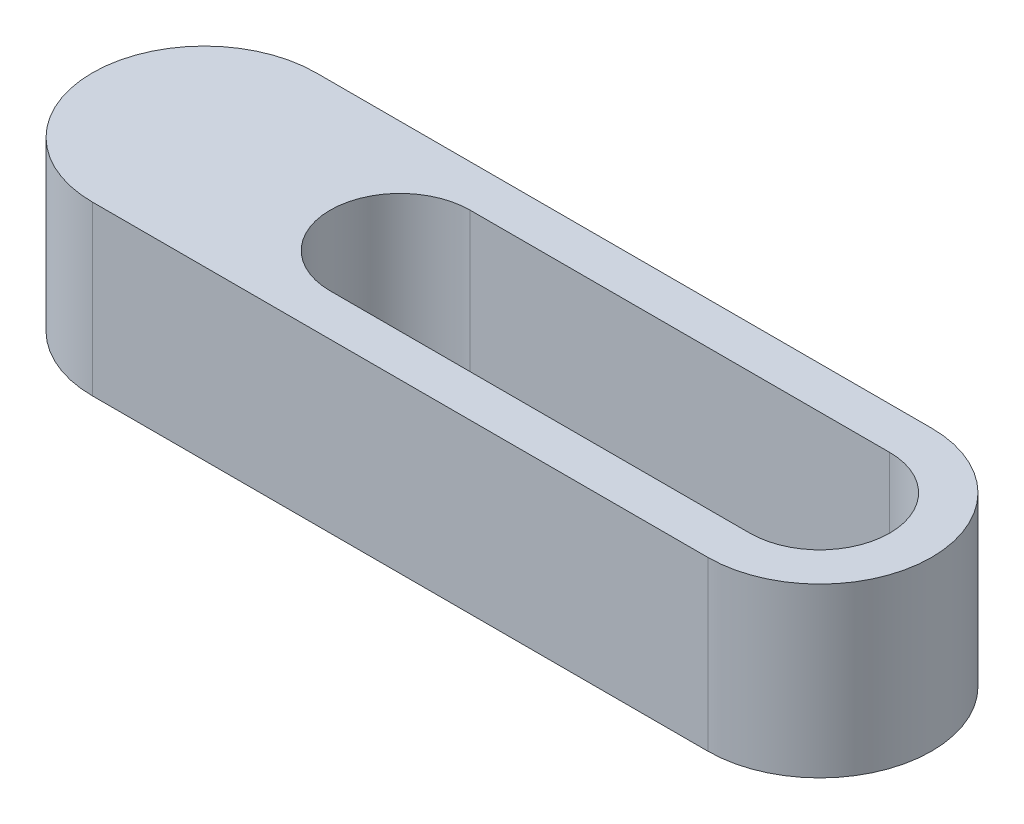
SolidWorks part; units mm, degrees
ref_plane "Ön Düzlem" through (0, 0, 0) normal (0, 0, 1) x (1, 0, 0)
ref_plane "Üst Düzlem" through (0, 0, 0) normal (0, 1, 0) x (1, 0, 0)
ref_plane "Sağ Düzlem" through (0, 0, 0) normal (1, 0, 0) x (0, 0, -1)
sketch "Çizim1" plane through (0, 0, 0) normal (0, 1, 0) x (1, 0, 0)
  line L1 (-5.5, 11.25) -> (5.5, 11.25)
  line L2 (-6, 10.75) -> (-6, -10.75)
  line L3 (-5.5, -11.25) -> (5.5, -11.25)
  line L4 (6, 10.75) -> (6, -10.75)
  line L5 (-6, 11.25) -> (6, -11.25) construction
  line L6 (-6, -11.25) -> (6, 11.25) construction
  arc A0 (5.5, -11.25) -> (6, -10.75) centre (5.5, -10.75) ccw
  arc A1 (-6, -10.75) -> (-5.5, -11.25) centre (-5.5, -10.75) ccw
  arc A2 (5.5, 11.25) -> (6, 10.75) centre (5.5, 10.75) cw
  arc A3 (-5.5, 11.25) -> (-6, 10.75) centre (-5.5, 10.75) ccw
  point P0 (0, 0)
  dimension "D3" = 0.5
  dimension "D1" = 12
  dimension "D2" = 22.5
extrude "Yükseklik-Ekstrüzyon1" add sketch "Çizim1" along normal blind 1
sketch "Çizim2" plane through (0, 1, 0) normal (0, 1, 0) x (1, 0, 0)
  line L0 (-5, 9.25) -> (-5, -9.25)
  line L1 (-5.5, 11.25) -> (5.5, 11.25)
  line L2 (-6, 10.75) -> (-6, -10.75)
  line L3 (-5.5, -11.25) -> (5.5, -11.25)
  line L4 (6, 10.75) -> (6, -10.75)
  line L5 (-6, 11.25) -> (-5.8961, 11.0552) construction
  line L6 (-6, -11.25) -> (-5.8961, -11.0552) construction
  line L7 (-4, -10.25) -> (4, -10.25)
  line L8 (5, 9.25) -> (5, -9.25)
  line L9 (-4, 10.25) -> (4, 10.25)
  line L10 (-6, -11.25) -> (6, -11.25) construction
  line L11 (6, 11.25) -> (6, -11.25) construction
  line L12 (-6, 11.25) -> (-6, -11.25) construction
  line L13 (-6, 11.25) -> (6, 11.25) construction
  line L14 (-5, 10.25) -> (5, 10.25) construction
  line L15 (-5, 10.25) -> (-5, -10.25) construction
  line L16 (-4.9345, 9.2521) -> (4.9345, -9.2521) construction
  line L17 (5, 10.25) -> (5, -10.25) construction
  line L18 (5.8961, 11.0552) -> (6, 11.25) construction
  line L19 (-5, -10.25) -> (5, -10.25) construction
  line L20 (5.8961, -11.0552) -> (6, -11.25) construction
  line L21 (-4.9345, -9.2521) -> (4.9345, 9.2521) construction
  arc A0 (5.5, -11.25) -> (6, -10.75) centre (5.5, -10.75) ccw
  arc A1 (-6, -10.75) -> (-5.5, -11.25) centre (-5.5, -10.75) ccw
  arc A2 (5.5, 11.25) -> (6, 10.75) centre (5.5, 10.75) cw
  arc A3 (-5.5, 11.25) -> (-6, 10.75) centre (-5.5, 10.75) ccw
  arc A5 (4, 10.25) -> (5, 9.25) centre (5, 10.25) ccw
  arc A7 (-4, -10.25) -> (-5, -9.25) centre (-5, -10.25) ccw
  arc A8 (-5, 9.25) -> (-4, 10.25) centre (-5, 10.25) ccw
  arc A9 (5, -9.25) -> (4, -10.25) centre (5, -10.25) ccw
  point P0 (0, 0)
  dimension "D2" = 0.5
  dimension "D1" = 1
extrude "Yükseklik-Ekstrüzyon2" add sketch "Çizim2" along normal blind 5
sketch "Çizim3" plane through (0, 6, 0) normal (0, 1, 0) x (1, 0, 0)
  line L0 (0, -10.25) -> (0, -11.25) construction
  line L1 (-4, -10.25) -> (4, -10.25) construction
  line L2 (-5.5, -11.25) -> (5.5, -11.25) construction
  line L3 (0, -11.25) -> (0, -10.75) construction
  line L4 (0, -10.75) -> (2.4368, -10.75) construction
  line L6 (-2, -10.25) -> (2, -10.25)
  line L7 (-2, -10.25) -> (-2, -11.25)
  line L8 (-2, -11.25) -> (2, -11.25)
  line L9 (2, -10.25) -> (2, -11.25)
  line L10 (-2, -10.25) -> (2, -11.25) construction
  line L11 (-2, -11.25) -> (2, -10.25) construction
  dimension "D1" = 4
extrude "Kes-Ekstrüzyon1" cut sketch "Çizim3" against normal blind 1
fillet "Radyus1" radius 0.1 2 edges at (2, 5, 10.75) (-2, 5, 10.75)
sketch "Çizim4" plane through (0, 6, 0) normal (0, 1, 0) x (1, 0, 0)
  line L0 (-4, 10.25) -> (4, 10.25)
  line L1 (-5.5, 11.25) -> (5.5, 11.25)
  line L2 (-6, 10.75) -> (-6, -10.75)
  line L3 (-5.5, -11.25) -> (5.5, -11.25)
  line L4 (6, 10.75) -> (6, -10.75)
  line L5 (-6, 11.25) -> (-5.8961, 11.0552) construction
  line L6 (-6, -11.25) -> (-5.8961, -11.0552) construction
  line L7 (-4, 10.25) -> (4, 10.25)
  line L8 (5, 9.25) -> (5, -9.25)
  line L9 (5, -9.25) -> (5, 9.25)
  line L10 (-4, 10.25) -> (4, 10.25)
  line L11 (5, 9.25) -> (5, -9.25)
  line L12 (-4, -10.25) -> (4, -10.25)
  line L13 (-5, 9.25) -> (-5, -9.25)
  line L14 (-4.9345, 9.2521) -> (4.9345, -9.2521) construction
  line L15 (-5, 10.25) -> (-5, -10.25) construction
  line L16 (-5, 10.25) -> (5, 10.25) construction
  line L17 (5, 10.25) -> (5, -10.25) construction
  line L18 (5.8961, 11.0552) -> (6, 11.25) construction
  line L19 (5.8961, -11.0552) -> (6, -11.25) construction
  line L20 (-5, -10.25) -> (5, -10.25) construction
  line L21 (-4.9345, -9.2521) -> (4.9345, 9.2521) construction
  arc A0 (5.5, -11.25) -> (6, -10.75) centre (5.5, -10.75) ccw
  arc A1 (-6, -10.75) -> (-5.5, -11.25) centre (-5.5, -10.75) ccw
  arc A2 (5.5, 11.25) -> (6, 10.75) centre (5.5, 10.75) cw
  arc A3 (-5.5, 11.25) -> (-6, 10.75) centre (-5.5, 10.75) ccw
  arc A4 (-5, 9.25) -> (-4, 10.25) centre (-5, 10.25) ccw
  arc A5 (4, 10.25) -> (5, 9.25) centre (5, 10.25) ccw
  arc A6 (-4, -10.25) -> (-5, -9.25) centre (-5, -10.25) ccw
  arc A7 (5, -9.25) -> (4, -10.25) centre (5, -10.25) ccw
  arc A8 (5, 10.25) -> (5, 10.25) centre (5, 10.25) cw
  arc A9 (5, -10.25) -> (5, -10.25) centre (5, -10.25) ccw
  arc A10 (-5, -10.25) -> (-5, -10.25) centre (-5, -10.25) ccw
  arc A11 (-5, 10.25) -> (-5, 10.25) centre (-5, 10.25) ccw
  point P0 (0, 0)
  line M12 (4, -10.25) -> (2, -10.25)
  line M14 (2, -11.25) -> (5.5, -11.25)
  arc M15 (5.5, -11.25) -> (6, -10.75) centre (5.5, -10.75) ccw
  line M16 (6, -10.75) -> (6, 10.75)
  arc M17 (6, 10.75) -> (5.5, 11.25) centre (5.5, 10.75) ccw
  line M18 (5.5, 11.25) -> (-5.5, 11.25)
  arc M19 (-5.5, 11.25) -> (-6, 10.75) centre (-5.5, 10.75) ccw
  line M20 (-6, 10.75) -> (-6, -10.75)
  arc M21 (-6, -10.75) -> (-5.5, -11.25) centre (-5.5, -10.75) ccw
  line M22 (-5.5, -11.25) -> (-2, -11.25)
  line M24 (-2, -10.25) -> (-4, -10.25)
  arc M25 (-4, -10.25) -> (-5, -9.25) centre (-5, -10.25) ccw
  line M26 (-5, -9.25) -> (-5, 9.25)
  arc M27 (-5, 9.25) -> (-4, 10.25) centre (-5, 10.25) ccw
  line M28 (-4, 10.25) -> (4, 10.25)
  arc M29 (4, 10.25) -> (5, 9.25) centre (5, 10.25) ccw
  line M30 (5, 9.25) -> (5, -9.25)
  arc M31 (5, -9.25) -> (4, -10.25) centre (5, -10.25) ccw
  dimension "D1" = 0.5
  dimension "D2" = 1
extrude "Yükseklik-Ekstrüzyon4" add sketch "Çizim4" along normal blind 9 contours M31 M12 M14 M15 M16 M17 M18 M19 M20 M21 M22 M24 M25 M26 M27 M28 M29 M30 | L12 L3 region at (0, 6, -10.995)
sketch "Çizim6" plane through (0, 15, 0) normal (0, 1, 0) x (1, 0, 0)
  line L0 (0, -10.25) -> (0, -12.25) construction
  line L1 (-5.5, 16) -> (-0.7, 16)
  line L2 (-6, 15.5) -> (-6, -15.5)
  line L3 (-5.5, -16) -> (-0.7, -16)
  line L4 (6, 15.5) -> (6, -15.5)
  line L5 (-6, 16) -> (6, -16) construction
  line L6 (-3.8437, -10.25) -> (6, 16) construction
  line L7 (-4, 10.25) -> (4, 10.25)
  line L8 (-5, 9.25) -> (-5, -9.25)
  line L9 (-4, -10.25) -> (4, -10.25)
  line L10 (5, 9.25) -> (5, -9.25)
  line L11 (-4.5616, 9.3512) -> (4.5616, -9.3512) construction
  line L12 (-4.5616, -9.3512) -> (4.5616, 9.3512) construction
  line L13 (0, -12.25) -> (0, -11.25) construction
  line L14 (-5.5, -11.25) -> (5.5, -11.25) construction
  line L15 (0, -11.25) -> (8.7476, -11.25) construction
  line L16 (0, -12.25) -> (8.7476, -12.25) construction
  line L17 (0.7, -16) -> (5.5, -16)
  line L18 (-0.5, -14.2247) -> (-0.5, -15.8)
  line L19 (0.5, -14.2247) -> (0.5, -15.8)
  line L20 (0, 0) -> (5, 0) construction
  line L21 (0.5, 14.2247) -> (0.5, 15.8)
  line L22 (-0.5, 14.2247) -> (-0.5, 15.8)
  line L23 (0.7, 16) -> (5.5, 16)
  arc A0 (-5, 9.25) -> (-4, 10.25) centre (-5, 10.25) ccw
  arc A1 (4, 10.25) -> (5, 9.25) centre (5, 10.25) ccw
  arc A2 (5, -9.25) -> (4, -10.25) centre (5, -10.25) ccw
  arc A3 (-4, -10.25) -> (-5, -9.25) centre (-5, -10.25) ccw
  arc A4 (5.5, -16) -> (6, -15.5) centre (5.5, -15.5) ccw
  arc A5 (-6, -15.5) -> (-5.5, -16) centre (-5.5, -15.5) ccw
  arc A6 (5.5, 16) -> (6, 15.5) centre (5.5, 15.5) cw
  arc A7 (-5.5, 16) -> (-6, 15.5) centre (-5.5, 15.5) ccw
  arc A9 (0.5833, -14.0622) -> (-0.5833, -14.0622) centre (0, -13.25) ccw
  arc A10 (0.5, -14.2247) -> (0.5833, -14.0622) centre (0.7, -14.2247) cw
  arc A11 (-0.5, -14.2247) -> (-0.5833, -14.0622) centre (-0.7, -14.2247) ccw
  arc A12 (0.5, -15.8) -> (0.7, -16) centre (0.7, -15.8) ccw
  arc A13 (-0.5, -15.8) -> (-0.7, -16) centre (-0.7, -15.8) cw
  arc A14 (0.5, 15.8) -> (0.7, 16) centre (0.7, 15.8) cw
  arc A15 (-0.5, 15.8) -> (-0.7, 16) centre (-0.7, 15.8) ccw
  arc A16 (0.5, 14.2247) -> (0.5833, 14.0622) centre (0.7, 14.2247) ccw
  arc A17 (-0.5, 14.2247) -> (-0.5833, 14.0622) centre (-0.7, 14.2247) cw
  arc A18 (0.5833, 14.0622) -> (-0.5833, 14.0622) centre (0, 13.25) cw
  point P0 (0, 0)
  point P6 (0, 0)
  point P54 (0.5, -16)
  dimension "D2" = 0.5
  dimension "D4" = 2
  dimension "D5" = 0.2
  dimension "D1" = 32
  dimension "D3" = 1
extrude "Yükseklik-Ekstrüzyon5" add sketch "Çizim6" along normal blind 2.5
sketch "Çizim7" plane through (0, 17.5, 0) normal (0, 1, 0) x (1, 0, 0)
  line L0 (6, -15.5) -> (6, 15.5) construction
  line L1 (-5.5, 11.25) -> (5.5, 11.25)
  line L2 (-6, 10.75) -> (-6, -10.75)
  line L3 (-5.5, -11.25) -> (5.5, -11.25)
  line L4 (6, 10.75) -> (6, -10.75)
  line L5 (-6, 11.25) -> (-5.8961, 11.0552) construction
  line L6 (-6, -11.25) -> (-5.8961, -11.0552) construction
  line L7 (-5, 9.25) -> (-5, -9.25)
  line L8 (-4, 10.25) -> (4, 10.25)
  line L9 (5, 9.25) -> (5, -9.25)
  line L10 (4, -10.25) -> (-4, -10.25)
  line L12 (-4.9345, 9.2521) -> (4.9345, -9.2521) construction
  line L13 (5.8961, 11.0552) -> (6, 11.25) construction
  line L14 (5.8961, -11.0552) -> (6, -11.25) construction
  line L15 (-5, -9.25) -> (-5, 9.25)
  line L16 (-4.9345, -9.2521) -> (4.9345, 9.2521) construction
  line L17 (-5, 9.25) -> (-5, -9.25)
  arc A0 (-6, -10.75) -> (-5.5, -11.25) centre (-5.5, -10.75) ccw
  arc A1 (5.5, -11.25) -> (6, -10.75) centre (5.5, -10.75) ccw
  arc A2 (5.5, 11.25) -> (6, 10.75) centre (5.5, 10.75) cw
  arc A3 (-5.5, 11.25) -> (-6, 10.75) centre (-5.5, 10.75) ccw
  arc A4 (-5, 9.25) -> (-4, 10.25) centre (-5, 10.25) ccw
  arc A5 (4, 10.25) -> (5, 9.25) centre (5, 10.25) ccw
  arc A6 (5, -9.25) -> (4, -10.25) centre (5, -10.25) ccw
  arc A8 (-4, -10.25) -> (-5, -9.25) centre (-5, -10.25) ccw
  point P0 (0, 0)
  line M16 (6, -15.5) -> (6, 15.5)
  line M28 (-6, 15.5) -> (-6, -15.5)
  line M39 (-5, -9.25) -> (-5, 9.25)
  arc M40 (-5, 9.25) -> (-4, 10.25) centre (-5, 10.25) ccw
  line M41 (-4, 10.25) -> (4, 10.25)
  arc M42 (4, 10.25) -> (5, 9.25) centre (5, 10.25) ccw
  line M43 (5, 9.25) -> (5, -9.25)
  arc M44 (5, -9.25) -> (4, -10.25) centre (5, -10.25) ccw
  line M45 (4, -10.25) -> (-4, -10.25)
  arc M46 (-4, -10.25) -> (-5, -9.25) centre (-5, -10.25) ccw
  dimension "D2" = 0.5
  dimension "D1" = 22.5
extrude "Yükseklik-Ekstrüzyon6" add sketch "Çizim7" along normal blind 3.5 contours L1 A3 A0 L3 A1 A2 M28 M16 M46 M39 M40 M41 M42 M43 M44 M45 region at (0, 17.5, -10.995)
sketch "Çizim8" plane through (0, 21, 0) normal (0, 1, 0) x (1, 0, 0)
  line L0 (6, -15.5) -> (6, -10.75) construction
  line L1 (-5.5, 11.25) -> (5.5, 11.25)
  line L2 (-6, 10.75) -> (-6, -10.75)
  line L3 (-5.5, -11.25) -> (5.5, -11.25)
  line L4 (6, 10.75) -> (6, -10.75)
  line L5 (-6, 11.25) -> (6, -11.25) construction
  line L6 (-6, -11.25) -> (6, 11.25) construction
  arc A0 (-6, -10.75) -> (-5.5, -11.25) centre (-5.5, -10.75) ccw
  arc A1 (5.5, -11.25) -> (6, -10.75) centre (5.5, -10.75) ccw
  arc A2 (5.5, 11.25) -> (6, 10.75) centre (5.5, 10.75) cw
  arc A3 (-5.5, 11.25) -> (-6, 10.75) centre (-5.5, 10.75) ccw
  point P0 (0, 0)
  dimension "D1" = 0.5
extrude "Yükseklik-Ekstrüzyon7" add sketch "Çizim8" along normal blind 1
sketch "Çizim9" plane through (0, 22, 0) normal (0, 1, 0) x (1, 0, 0)
  line L0 (-6, 5.25) -> (6, 5.25) construction
  line L1 (-6, 10.75) -> (-6, -10.75) construction
  line L2 (6, -10.75) -> (6, 10.75) construction
  line L3 (5.5, 11.25) -> (-5.5, 11.25) construction
  line L4 (0, 5.25) -> (0, -0.75) construction
  arc A0 (2.4451, -0.2292) -> (-2.4451, -0.2292) centre (0, 5.25) ccw
  arc A1 (-2.4451, -0.2292) -> (2.4451, -0.2292) centre (0, -0.75) ccw
  arc A2 (1.0153, 0.3542) -> (-1.0153, 0.3542) centre (0, 5.25) ccw
  arc A3 (-1.0153, 0.3542) -> (1.0153, 0.3542) centre (0, -0.75) ccw
  dimension "D2" = 5
  dimension "D1" = 6
  dimension "D3" = 1
extrude "Kes-Ekstrüzyon2" cut sketch "Çizim9" against normal blind 1 contours A2 A3
extrude "Yükseklik-Ekstrüzyon8" add sketch "Çizim9<3>" along normal blind 3
sketch "Çizim9<3>" plane through (0, 22, 0) normal (0, 1, 0) x (1, 0, 0) same geometry as "Çizim9"
fillet "Radyus2" radius 0.5 2 edges at (1.0153, 23, -0.3542) (-1.0153, 23, -0.3542)
sketch "Çizim10" plane through (0, 25, 0) normal (0, 1, 0) x (1, 0, 0)
  arc A0 (2.4451, -0.2292) -> (-2.4451, -0.2292) centre (0, 5.25) ccw
  arc A1 (-2.4451, -0.2292) -> (2.4451, -0.2292) centre (0, -0.75) ccw
extrude "Yükseklik-Ekstrüzyon9" add sketch "Çizim10" along normal blind 1
sketch "Çizim11" plane through (0, 26, 0) normal (0, 1, 0) x (1, 0, 0)
  circle A0 centre (0, 5.25) radius 2.5
  dimension "D1" = 5
extrude "Kes-Ekstrüzyon3" cut sketch "Çizim11" against normal blind 10
sketch "Çizim15" plane through (0, 26, 0) normal (0, 1, 0) x (1, 0, 0)
  circle A0 centre (0, -0.75) radius 0.25
  dimension "D1" = 0.5
extrude "Yükseklik-Ekstrüzyon12" add sketch "Çizim15" against normal blind 11
ref_plane "Düzlem3" through (0, 30, 0) normal (0, 1, 0) x (1, 0, 0)
sketch "Çizim19" plane through (0, 30, 0) normal (0, 1, 0) x (1, 0, 0)
  circle A0 centre (0, 5.25) radius 2.25
  dimension "D1" = 4.5
extrude "Yükseklik-Ekstrüzyon17" add sketch "Çizim19" against normal blind 5 separate body
sketch "Çizim20" plane through (0, 25, 0) normal (0, -1, 0) x (1, 0, 0)
  circle A0 centre (0, -5.25) radius 4.75
  dimension "D1" = 9.5
extrude "Yükseklik-Ekstrüzyon18" add sketch "Çizim20" along normal blind 3
sketch "Çizim21" plane through (0, 30, 0) normal (0, 1, 0) x (1, 0, 0)
  circle A0 centre (0, 5.25) radius 0.75
  dimension "D1" = 1.5
extrude "Kes-Ekstrüzyon5" cut sketch "Çizim21" against normal blind 10
ref_plane "Düzlem4" through (0, 25.5, 0) normal (0, 1, 0) x (1, 0, 0)
sketch "Çizim22" plane through (0, 25.5, 0) normal (0, 1, 0) x (1, 0, 0)
  line L0 (0, 11.25) -> (0, -3.25) construction
  arc A0 (2.4451, -0.2292) -> (-2.4451, -0.2292) centre (0, 5.25) ccw construction
  arc A1 (-2.4451, -0.2292) -> (2.4451, -0.2292) centre (0, -0.75) ccw construction
  circle A2 centre (0, -0.75) radius 0.5
  dimension "D1" = 1
extrude "Yükseklik-Ekstrüzyon19" add sketch "Çizim22" against normal blind 5
sketch "Çizim23" plane through (0, 20.5, 0) normal (0, -1, 0) x (1, 0, 0)
  circle A0 centre (0, 0.75) radius 4
  dimension "D1" = 8
extrude "Yükseklik-Ekstrüzyon20" add sketch "Çizim23" along normal blind 2
sketch "Çizim24" plane through (0, 22, 0) normal (0, -1, 0) x (1, 0, 0)
  circle A0 centre (0, -5.25) radius 0.75
extrude "Yükseklik-Ekstrüzyon21" add sketch "Çizim24" along normal blind 7 separate body
ref_plane "Düzlem5" through (0, 19, 0) normal (0, -1, 0) x (-1, 0, 0)
sketch "Çizim25" plane through (0, 19, 0) normal (0, -1, 0) x (-1, 0, 0)
  circle A0 centre (0, 5.25) radius 3.5
  dimension "D1" = 7
extrude "Yükseklik-Ekstrüzyon22" add sketch "Çizim25" along normal blind 1
ref_plane "Düzlem6" through (0, 17.5, 0) normal (0, -1, 0) x (-1, 0, 0)
sketch "Çizim26" plane through (0, 17.5, 0) normal (0, -1, 0) x (-1, 0, 0)
  circle A0 centre (0, -0.75) radius 4.5
  dimension "D1" = 9
extrude "Yükseklik-Ekstrüzyon23" add sketch "Çizim26" along normal blind 1
sketch "Çizim32" plane through (0, 0, 10.25) normal (0, 0, -1) x (-1, 0, 0)
  line L1 (2, 6) -> (-2, 6)
  line L2 (2, 6) -> (2, 5.1)
  line L3 (1.9, 5) -> (-1.9, 5)
  line L4 (-2, 6) -> (-2, 5.1)
  arc A0 (-1.9, 5) -> (-2, 5.1) centre (-1.9, 5.1) cw
  arc A1 (2, 5.1) -> (1.9, 5) centre (1.9, 5.1) cw
  point P7 (-2, 5)
  dimension "D3" = 0.1
  dimension "D1" = 1
  dimension "D2" = 4
extrude "Kes-Ekstrüzyon7" cut sketch "Çizim32" along normal blind 30
sketch "Çizim33" plane through (0, 0, 11.25) normal (0, 0, 1) x (1, 0, 0)
  line L1 (-2, 6) -> (2, 6)
  line L2 (-2, 6) -> (-2, 5.1)
  line L3 (-1.9, 5) -> (1.9, 5)
  line L4 (2, 6) -> (2, 5.1)
  arc A0 (1.9, 5) -> (2, 5.1) centre (1.9, 5.1) ccw
  arc A1 (-2, 5.1) -> (-1.9, 5) centre (-1.9, 5.1) ccw
  point P7 (2, 5)
  point P10 (-2, 5)
  dimension "D3" = 0.1
  dimension "D1" = 1
  dimension "D2" = 4
extrude "Yükseklik-Ekstrüzyon33" add sketch "Çizim33" against normal blind 1
sketch "Çizim34" plane through (0, 1, 0) normal (0, 1, 0) x (1, 0, 0)
  line L0 (-5, -6.25) -> (5, -6.25) construction
  line L1 (-5, 9.25) -> (-5, -9.25) construction
  line L2 (5, -9.25) -> (5, 9.25) construction
  line L3 (-4, -10.25) -> (4, -10.25) construction
  line L5 (-3, -3.25) -> (3, -3.25)
  line L6 (-4, -4.25) -> (-4, -8.25)
  line L7 (-3, -9.25) -> (3, -9.25)
  line L8 (4, -4.25) -> (4, -8.25)
  line L9 (-4, -3.25) -> (4, -9.25) construction
  line L10 (-4, -9.25) -> (4, -3.25) construction
  arc A0 (3, -9.25) -> (4, -8.25) centre (3, -8.25) ccw
  arc A1 (-4, -8.25) -> (-3, -9.25) centre (-3, -8.25) ccw
  arc A2 (3, -3.25) -> (4, -4.25) centre (3, -4.25) cw
  arc A3 (-3, -3.25) -> (-4, -4.25) centre (-3, -4.25) ccw
  point P8 (0, -6.25)
  dimension "D4" = 1
  dimension "D1" = 4
  dimension "D2" = 6
  dimension "D3" = 8
extrude "Yükseklik-Ekstrüzyon34" add sketch "Çizim34" along normal blind 14
ref_plane "Düzlem8" through (0, 1, 0) normal (0, -1, 0) x (-1, 0, 0)
sketch "Çizim37" plane through (0, 1, 0) normal (0, -1, 0) x (-1, 0, 0)
  line L0 (4, -6.25) -> (-4, -6.25) construction
  line L1 (4, -4.25) -> (4, -8.25) construction
  line L2 (-4, -8.25) -> (-4, -4.25) construction
  line L4 (4, -9.25) -> (-4, -9.25)
  line L5 (4, -9.25) -> (4, -3.25)
  line L6 (4, -3.25) -> (-4, -3.25)
  line L7 (-4, -9.25) -> (-4, -3.25)
  line L8 (4, -9.25) -> (-4, -3.25) construction
  line L9 (4, -3.25) -> (-4, -9.25) construction
  point P6 (0, -6.25)
  dimension "D1" = 6
  dimension "D2" = 8
extrude "Yükseklik-Ekstrüzyon36" add sketch "Çizim37" against normal blind 1
ref_plane "Düzlem9" through (0, 0, -10.75) normal (0, 0, -1) x (-1, 0, 0)
sketch "Çizim39" plane through (0, 0, -10.75) normal (0, 0, -1) x (-1, 0, 0)
  line L0 (0, 0) -> (0, 6.0146) construction
  line L1 (-5.5, 0) -> (5.5, 0) construction
  line L2 (-2, 6.0146) -> (2, 6.0146)
  line L4 (-2, 6.0146) -> (-2, 5.0146)
  line L5 (-2, 5.0146) -> (2, 5.0146)
  line L6 (2, 6.0146) -> (2, 5.0146)
  line L7 (0, 6.0146) -> (2, 5.0146) construction
  line L8 (-2, 5.0146) -> (0, 6.0146) construction
extrude "Yükseklik-Ekstrüzyon37" add sketch "Çizim39" along normal blind 0.1
sketch "Çizim40" plane through (0, 0, -10.85) normal (0, 0, -1) x (-1, 0, 0)
  line L0 (-2, 5.55) -> (2, 5.55) construction
  line L1 (-2, 6) -> (-2, 5.1) construction
  line L2 (2, 5.1) -> (2, 6) construction
  circle A0 centre (0, 5.55) radius 0.4
  circle A1 centre (1, 5.55) radius 0.4
  circle A2 centre (-1, 5.55) radius 0.4
  dimension "D1" = 0.8
  dimension "D2" = 1
  dimension "D3" = 1
extrude "Yükseklik-Ekstrüzyon38" add sketch "Çizim40" along normal blind 2
sketch "Çizim41" plane through (0, 30, 0) normal (0, 1, 0) x (1, 0, 0)
  line L0 (0, 5.25) -> (-2.25, 5.25) construction
  circle A0 centre (0, 5.25) radius 2.25
  circle A1 centre (-2.25, 5.25) radius 0.15
  circle A2 centre (-2.2138, 5.6518) radius 0.15
  circle A3 centre (-2.1065, 6.0406) radius 0.15
  circle A4 centre (-1.9315, 6.404) radius 0.15
  circle A5 centre (-1.6944, 6.7304) radius 0.15
  circle A6 centre (-1.4029, 7.0091) radius 0.15
  circle A7 centre (-1.0662, 7.2313) radius 0.15
  circle A8 centre (-0.6953, 7.3899) radius 0.15
  circle A9 centre (-0.302, 7.4796) radius 0.15
  circle A10 centre (0.1009, 7.4977) radius 0.15
  circle A11 centre (0.5007, 7.4436) radius 0.15
  circle A12 centre (0.8843, 7.3189) radius 0.15
  circle A13 centre (1.2395, 7.1278) radius 0.15
  circle A14 centre (1.5549, 6.8763) radius 0.15
  circle A15 centre (1.8203, 6.5725) radius 0.15
  circle A16 centre (2.0272, 6.2262) radius 0.15
  circle A17 centre (2.1689, 5.8486) radius 0.15
  circle A18 centre (2.2409, 5.4517) radius 0.15
  circle A19 centre (2.2409, 5.0483) radius 0.15
  circle A20 centre (2.1689, 4.6514) radius 0.15
  circle A21 centre (2.0272, 4.2738) radius 0.15
  circle A22 centre (1.8203, 3.9275) radius 0.15
  circle A23 centre (1.5549, 3.6237) radius 0.15
  circle A24 centre (1.2395, 3.3722) radius 0.15
  circle A25 centre (0.8843, 3.1811) radius 0.15
  circle A26 centre (0.5007, 3.0564) radius 0.15
  circle A27 centre (0.1009, 3.0023) radius 0.15
  circle A28 centre (-0.302, 3.0204) radius 0.15
  circle A29 centre (-0.6953, 3.1101) radius 0.15
  circle A30 centre (-1.0662, 3.2687) radius 0.15
  circle A31 centre (-1.4029, 3.4909) radius 0.15
  circle A32 centre (-1.6944, 3.7696) radius 0.15
  circle A33 centre (-1.9315, 4.096) radius 0.15
  circle A34 centre (-2.1065, 4.4594) radius 0.15
  circle A35 centre (-2.2138, 4.8482) radius 0.15
  point P75 (0, 5.25)
  circle M3 centre (0, 5.25) radius 2.25
  dimension "D1" = 0.3
  dimension "D2" = 35
extrude "Kes-Ekstrüzyon8" cut sketch "Çizim41" against normal blind 5 contours A1 A0 M3 | A1 L0 A0 | L0 A1 M3 | A3 | A2 | A35 | A34 | A33 | A32 | A31 | A30 | A29 | A28 | A27 | A26 | A25 | A24 | A23 | A22 | A21 | A20 | A19 | A18 | A17 | A16 | A15 | A14 | A13 | A12 | A11 | A10 | A9 | A8 | A7 | A6 | A5 | A4 region at (-2.1854, 30, -5.187) region at (-2.1854, 30, -5.313) region at (-2.3128, 30, -5.25)
sketch "Sketch1" plane through (0, 0, 0) normal (0, -1, 0) x (1, 0, 0)
  line L1 (-12.5223, 17.3189) -> (9.2962, 17.3189)
  line L2 (-12.5223, 17.3189) -> (-12.5223, -17.0642)
  line L3 (-12.5223, -17.0642) -> (9.2962, -17.0642)
  line L4 (9.2962, 17.3189) -> (9.2962, -17.0642)
extrude "Cut-Extrude1" cut sketch "Sketch1" against normal up to surface (26 mm away) up to face at (0, 26, -2.75)
sketch "Sketch2" plane through (0, 30, 0) normal (0, 1, 0) x (1, 0, 0)
  line L0 (0, 9.25) -> (22, 9.25)
  line L1 (0, 1.25) -> (22, 1.25)
  line L2 (7, 7.75) -> (22, 7.75)
  line L3 (7, 2.75) -> (22, 2.75)
  arc A0 (0, 9.25) -> (0, 1.25) centre (0, 5.25) ccw
  arc A1 (22, 1.25) -> (22, 9.25) centre (22, 5.25) ccw
  arc A2 (22, 2.75) -> (22, 7.75) centre (22, 5.25) ccw
  arc A3 (7, 7.75) -> (7, 2.75) centre (7, 5.25) ccw
  point P8 (0, 0)
  point P17 (0, 0)
  dimension "D1" = 8
  dimension "D2" = 5
  dimension "D3" = 7
  dimension "D4" = 22
extrude "Boss-Extrude1" add sketch "Sketch2" along normal blind 6
sketch "Sketch3" plane through (0, 26, 0) normal (0, -1, 0) x (1, 0, 0)
  arc A1 (-0.4499, -3.0454) -> (-0.1528, -3.0052) centre (-0.302, -3.0204) ccw
  arc A2 (-0.4499, -3.0454) -> (-0.1528, -3.0052) centre (-0.302, -3.0204) ccw construction
  arc A8 (-0.049, -3.0005) -> (-0.1528, -3.0052) centre (0, -5.25) ccw
  arc A11 (-0.049, -3.0005) -> (0.2505, -3.014) centre (0.1009, -3.0023) ccw
  arc A12 (0.3534, -3.0279) -> (0.2505, -3.014) centre (0, -5.25) ccw
  arc A13 (0.3534, -3.0279) -> (0.6457, -3.0946) centre (0.5007, -3.0564) ccw
  arc A14 (0.7445, -3.1267) -> (0.6457, -3.0946) centre (0, -5.25) ccw
  arc A15 (0.7445, -3.1267) -> (1.0202, -3.2446) centre (0.8843, -3.1811) ccw
  arc A16 (1.1116, -3.2938) -> (1.0202, -3.2446) centre (0, -5.25) ccw
  arc A17 (1.1116, -3.2938) -> (1.3619, -3.459) centre (1.2395, -3.3722) ccw
  arc A18 (1.4431, -3.5237) -> (1.3619, -3.459) centre (0, -5.25) ccw
  arc A19 (1.4431, -3.5237) -> (1.6598, -3.7309) centre (1.5549, -3.6237) ccw
  arc A20 (1.7281, -3.8091) -> (1.6598, -3.7309) centre (0, -5.25) ccw
  arc A21 (1.7281, -3.8091) -> (1.9044, -4.0517) centre (1.8203, -3.9275) ccw
  arc A22 (1.9576, -4.1409) -> (1.9044, -4.0517) centre (0, -5.25) ccw
  arc A23 (1.9576, -4.1409) -> (2.0877, -4.411) centre (2.0272, -4.2738) ccw
  arc A24 (2.1242, -4.5082) -> (2.0877, -4.411) centre (0, -5.25) ccw
  arc A25 (2.1242, -4.5082) -> (2.204, -4.7973) centre (2.1689, -4.6514) ccw
  arc A26 (2.2225, -4.8994) -> (2.204, -4.7973) centre (0, -5.25) ccw
  arc A27 (2.2225, -4.8994) -> (2.2494, -5.1981) centre (2.2409, -5.0483) ccw
  arc A28 (2.2494, -5.3019) -> (2.2494, -5.1981) centre (0, -5.25) ccw
  arc A29 (2.2494, -5.3019) -> (2.2225, -5.6006) centre (2.2409, -5.4517) ccw
  arc A30 (2.204, -5.7027) -> (2.2225, -5.6006) centre (0, -5.25) ccw
  arc A31 (2.204, -5.7027) -> (2.1242, -5.9918) centre (2.1689, -5.8486) ccw
  arc A32 (2.0877, -6.089) -> (2.1242, -5.9918) centre (0, -5.25) ccw
  arc A33 (2.0877, -6.089) -> (1.9576, -6.3591) centre (2.0272, -6.2262) ccw
  arc A34 (1.9044, -6.4483) -> (1.9576, -6.3591) centre (0, -5.25) ccw
  arc A35 (1.9044, -6.4483) -> (1.7281, -6.6909) centre (1.8203, -6.5725) ccw
  arc A36 (1.6598, -6.7691) -> (1.7281, -6.6909) centre (0, -5.25) ccw
  arc A37 (1.6598, -6.7691) -> (1.4431, -6.9763) centre (1.5549, -6.8763) ccw
  arc A38 (1.3619, -7.041) -> (1.4431, -6.9763) centre (0, -5.25) ccw
  arc A39 (1.3619, -7.041) -> (1.1116, -7.2062) centre (1.2395, -7.1278) ccw
  arc A40 (1.0202, -7.2554) -> (1.1116, -7.2062) centre (0, -5.25) ccw
  arc A41 (1.0202, -7.2554) -> (0.7445, -7.3733) centre (0.8843, -7.3189) ccw
  arc A42 (0.6457, -7.4054) -> (0.7445, -7.3733) centre (0, -5.25) ccw
  arc A43 (0.6457, -7.4054) -> (0.3534, -7.4721) centre (0.5007, -7.4436) ccw
  arc A44 (0.2505, -7.486) -> (0.3534, -7.4721) centre (0, -5.25) ccw
  arc A45 (0.2505, -7.486) -> (-0.049, -7.4995) centre (0.1009, -7.4977) ccw
  arc A46 (-0.1528, -7.4948) -> (-0.049, -7.4995) centre (0, -5.25) ccw
  arc A47 (-0.1528, -7.4948) -> (-0.4499, -7.4546) centre (-0.302, -7.4796) ccw
  arc A48 (-0.5512, -7.4314) -> (-0.4499, -7.4546) centre (0, -5.25) ccw
  arc A49 (-0.5512, -7.4314) -> (-0.8363, -7.3388) centre (-0.6953, -7.3899) ccw
  arc A50 (-0.9318, -7.298) -> (-0.8363, -7.3388) centre (0, -5.25) ccw
  arc A51 (-0.9318, -7.298) -> (-1.1959, -7.1559) centre (-1.0662, -7.2313) ccw
  arc A52 (-1.2825, -7.0987) -> (-1.1959, -7.1559) centre (0, -5.25) ccw
  arc A53 (-1.2825, -7.0987) -> (-1.5169, -6.9117) centre (-1.4029, -7.0091) ccw
  arc A54 (-1.592, -6.84) -> (-1.5169, -6.9117) centre (0, -5.25) ccw
  arc A55 (-1.592, -6.84) -> (-1.7893, -6.6142) centre (-1.6944, -6.7304) ccw
  arc A56 (-1.8503, -6.5302) -> (-1.7893, -6.6142) centre (0, -5.25) ccw
  arc A57 (-1.8503, -6.5302) -> (-2.0041, -6.2728) centre (-1.9315, -6.404) ccw
  arc A58 (-2.0492, -6.1792) -> (-2.0041, -6.2728) centre (0, -5.25) ccw
  arc A59 (-2.0492, -6.1792) -> (-2.1545, -5.8985) centre (-2.1065, -6.0406) ccw
  arc A60 (-2.1822, -5.7984) -> (-2.1545, -5.8985) centre (0, -5.25) ccw
  arc A61 (-2.1822, -5.7984) -> (-2.2357, -5.5034) centre (-2.2138, -5.6518) ccw
  arc A62 (-2.245, -5.3999) -> (-2.2357, -5.5034) centre (0, -5.25) ccw
  arc A63 (-2.245, -5.3999) -> (-2.245, -5.1001) centre (-2.25, -5.25) ccw
  arc A64 (-2.2357, -4.9966) -> (-2.245, -5.1001) centre (0, -5.25) ccw
  arc A65 (-2.2357, -4.9966) -> (-2.1822, -4.7016) centre (-2.2138, -4.8482) ccw
  arc A66 (-2.1545, -4.6015) -> (-2.1822, -4.7016) centre (0, -5.25) ccw
  arc A67 (-2.1545, -4.6015) -> (-2.0492, -4.3208) centre (-2.1065, -4.4594) ccw
  arc A68 (-2.0041, -4.2272) -> (-2.0492, -4.3208) centre (0, -5.25) ccw
  arc A69 (-2.0041, -4.2272) -> (-1.8503, -3.9698) centre (-1.9315, -4.096) ccw
  arc A70 (-1.7893, -3.8858) -> (-1.8503, -3.9698) centre (0, -5.25) ccw
  arc A71 (-1.7893, -3.8858) -> (-1.592, -3.66) centre (-1.6944, -3.7696) ccw
  arc A72 (-1.5169, -3.5883) -> (-1.592, -3.66) centre (0, -5.25) ccw
  arc A73 (-1.5169, -3.5883) -> (-1.2825, -3.4013) centre (-1.4029, -3.4909) ccw
  arc A74 (-1.1959, -3.3441) -> (-1.2825, -3.4013) centre (0, -5.25) ccw
  arc A75 (-1.1959, -3.3441) -> (-0.9318, -3.202) centre (-1.0662, -3.2687) ccw
  arc A76 (-0.8363, -3.1612) -> (-0.9318, -3.202) centre (0, -5.25) ccw
  arc A77 (-0.8363, -3.1612) -> (-0.5512, -3.0686) centre (-0.6953, -3.1101) ccw
  arc A78 (-0.4499, -3.0454) -> (-0.5512, -3.0686) centre (0, -5.25) ccw
  point P150 (0, -5.25)
  dimension "D1" = 35
extrude "Cut-Extrude2" cut sketch "Sketch3" against normal blind 8
